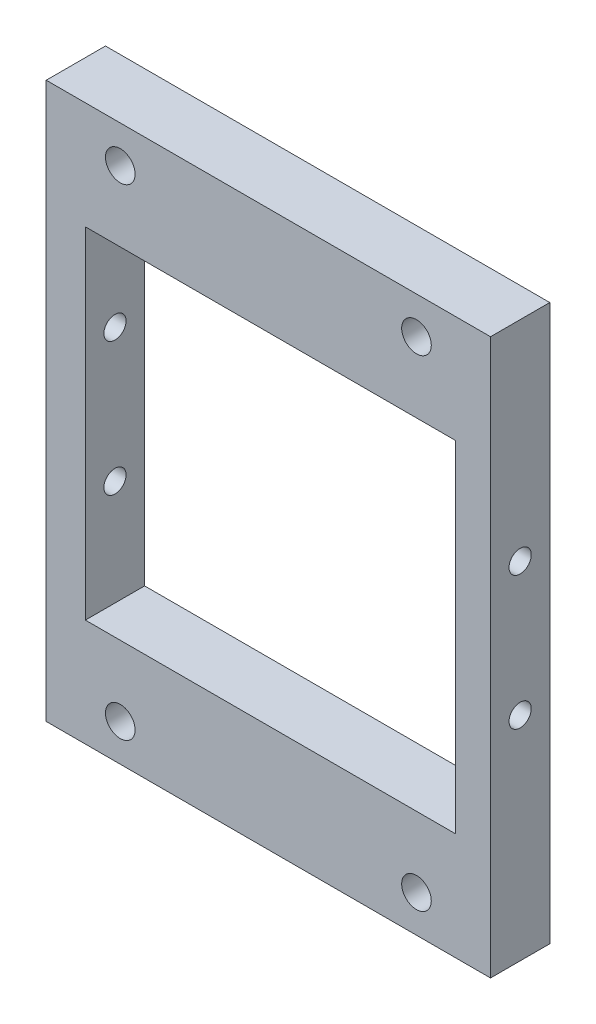
SolidWorks part; units mm, degrees
ref_plane "Front" through (0, 0, 0) normal (0, 0, 1) x (1, 0, 0)
ref_plane "Top" through (0, 0, 0) normal (0, 1, 0) x (1, 0, 0)
ref_plane "Right" through (0, 0, 0) normal (1, 0, 0) x (0, 0, -1)
sketch "草图1" plane through (0, 0, 0) normal (0, 0, 1) x (1, 0, 0)
  line L1 (-25.2871, -37.5) -> (-85.2871, -37.5)
  line L2 (-25.2871, -37.5) -> (-25.2871, 37.5)
  line L3 (-25.2871, 37.5) -> (-85.2871, 37.5)
  line L4 (-85.2871, -37.5) -> (-85.2871, 37.5)
  line L5 (-25.2871, -37.5) -> (-85.2871, 37.5) construction
  line L6 (-25.2871, 37.5) -> (-85.2871, -37.5) construction
  point P0 (-55.2871, 0)
  point P5 (-52.7829, 0)
  point P6 (-55.2871, -1.9215)
  point P7 (0, 0)
  dimension "D1" = 60
  dimension "D2" = 75
extrude "凸台-拉伸1" add sketch "草图1" along normal blind 8 contours L1 L4 L3 L2
sketch "草图2" plane through (0, 0, 8) normal (0, 0, 1) x (1, 0, 0)
  line L0 (-80, 17) -> (-80, 23) construction
  line L1 (-80, 17) -> (-80, -17) construction
  line L2 (-80, -23) -> (-80, -17) construction
  line L3 (-30, -23) -> (-80, -23) construction
  line L4 (-30, -23) -> (-30, -17) construction
  line L5 (-30, 17) -> (-30, -17) construction
  line L6 (-30, 17) -> (-30, 23) construction
  line L7 (-30, 23) -> (-80, 23) construction
  line L8 (-80, 17) -> (-80, 23)
  line L9 (-80, 17) -> (-80, -17)
  line L10 (-80, -23) -> (-80, -17)
  line L11 (-30, -23) -> (-80, -23)
  line L12 (-30, -23) -> (-30, -17)
  line L13 (-30, 17) -> (-30, -17)
  line L14 (-30, 17) -> (-30, 23)
  line L15 (-30, 23) -> (-80, 23)
extrude "切除-拉伸1" cut sketch "草图2" against normal up to surface (8 mm away)
sketch "草图3" plane through (0, 0, 8) normal (0, 0, 1) x (1, 0, 0)
  line L0 (-75.2871, -32.5) -> (-35.2871, -32.5) construction
  line L1 (-85.2871, -37.5) -> (-85.2871, 37.5) construction
  line L2 (-25.2871, -37.5) -> (-85.2871, -37.5) construction
  circle A0 centre (-75.2871, -32.5) radius 2
  circle A1 centre (-35.2871, -32.5) radius 2
  dimension "D3" = 4
  dimension "D1" = 10
  dimension "D2" = 40
  dimension "D4" = 5
extrude "切除-拉伸2" cut sketch "草图3" against normal blind 6
mirror "镜向1" about plane through (0, 0, 0) normal (0, 1, 0) of "切除-拉伸2"
sketch "草图4" plane through (-85.2871, 0, 0) normal (-1, 0, 0) x (0, 0, 1)
  line L0 (8, -37.5) -> (8, 37.5) construction
  circle A0 centre (4, -8.7474) radius 1.5
  circle A1 centre (4, 9.2526) radius 1.5
  point P4 (0, 0)
  point P7 (4, 9.2526)
  point P9 (4, 6.915)
  dimension "D1" = 3
  dimension "D2" = 4
  dimension "D3" = 18
extrude "切除-拉伸3" cut sketch "草图4" against normal through all
